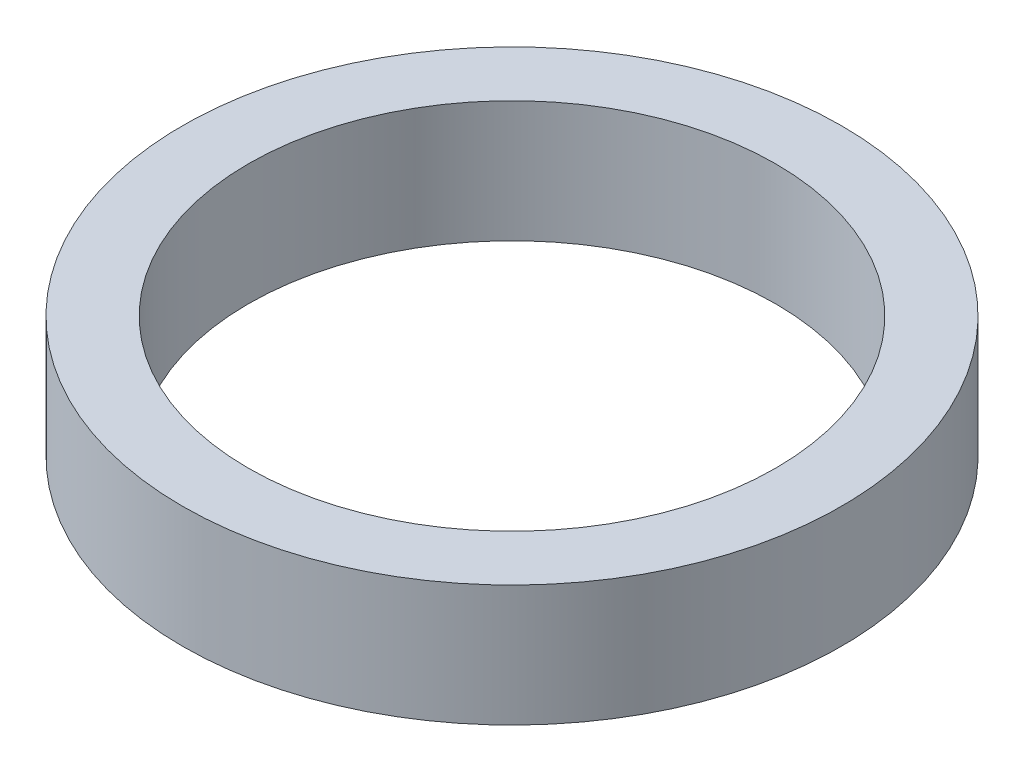
SolidWorks part; units mm, degrees
ref_plane "Front Plane" through (0, 0, 0) normal (0, 0, 1) x (1, 0, 0)
ref_plane "Top Plane" through (0, 0, 0) normal (0, 1, 0) x (1, 0, 0)
ref_plane "Right Plane" through (0, 0, 0) normal (1, 0, 0) x (0, 0, -1)
sketch "Sketch1" plane through (0, 0, 0) normal (0, 1, 0) x (1, 0, 0)
  circle A0 centre (0, 0) radius 62.5
  dimension "FLANGE_OD" = 125
extrude "Boss-Extrude1" add sketch "Sketch1" along normal blind 23
sketch "Sketch2" plane through (0, 0, 0) normal (0, 1, 0) x (1, 0, 0)
  circle A0 centre (0, 0) radius 50
  dimension "BORE_D" = 100
extrude "Cut-Extrude1" cut sketch "Sketch2" along normal through all
sketch "Sketch3" plane through (0, 23, 0) normal (0, 1, 0) x (1, 0, 0)
  circle A0 centre (0, 0) radius 28.1679 construction
  circle A1 centre (-28.1679, 0) radius 2.0107
  dimension "BOLT_D" = 4.0214
  dimension "BOLT_PCD" = 56.3358
extrude "Cut-Extrude2" cut sketch "Sketch3" against normal blind 18.6052 rebuild error yes
pattern_circular "CirPattern1" count 8 over 360 rebuild error yes
